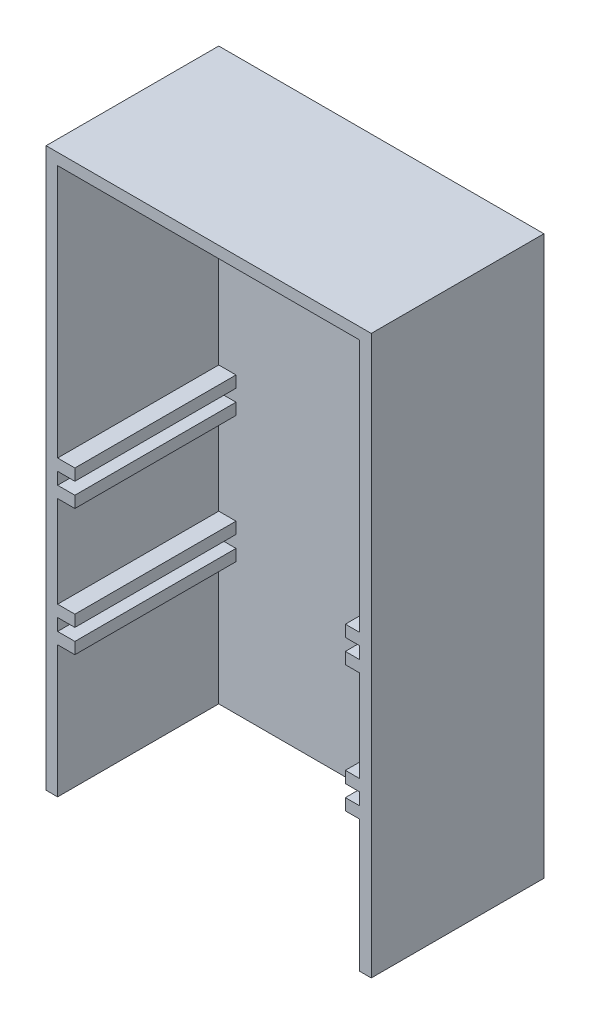
SolidWorks part; units mm, degrees
ref_plane "Front Plane" through (0, 0, 0) normal (0, 0, 1) x (1, 0, 0)
ref_plane "Top Plane" through (0, 0, 0) normal (0, 1, 0) x (1, 0, 0)
ref_plane "Right Plane" through (0, 0, 0) normal (1, 0, 0) x (0, 0, -1)
sketch "Sketch1" plane through (0, 0, 0) normal (0, 0, 1) x (1, 0, 0)
  line L1 (0, 0) -> (-56.5, 0)
  line L2 (0, 0) -> (0, 100)
  line L3 (0, 100) -> (-56.5, 100)
  line L4 (-56.5, 0) -> (-56.5, 100)
  dimension "D1" = 56.5
  dimension "D2" = 100
extrude "Boss-Extrude1" add sketch "Sketch1" along normal blind 30
shell "Shell1" thickness 2 removed face at (-28.25, 50, 30)
sketch "Sketch2" plane through (0, 0, 2) normal (0, 0, 1) x (1, 0, 0)
  line L0 (-54.5, 98) -> (-54.5, 2) construction
  line L1 (-54.5, 98) -> (-2, 98)
  line L2 (-54.5, 98) -> (-54.5, 96)
  line L3 (-54.5, 96) -> (-2, 96)
  line L4 (-2, 98) -> (-2, 96)
  line L5 (-2, 2) -> (-2, 98) construction
  line L7 (-2, 98) -> (-54.5, 98) construction
  dimension "D1" = 2
  dimension "D2" = 0
extrude "Boss-Extrude2" add sketch "Sketch2" along normal blind 26
sketch "Sketch3" plane through (0, 96, 0) normal (0, -1, 0) x (1, 0, 0)
  line L0 (-54.5, 28) -> (-2, 28) construction
  line L1 (-36.35, 28) -> (-20.15, 28)
  arc A0 (-20.15, 28) -> (-36.35, 28) centre (-28.25, 28) cw
  dimension "D1" = 8.1
extrude "Cut-Extrude5" cut sketch "Sketch3" against normal blind 3
sketch "Sketch6" plane through (-54.5, 0, 0) normal (1, 0, 0) x (0, 0, -1)
  line L0 (-30, 0) -> (-30, 100) construction
  line L1 (-30, 54) -> (0, 54)
  line L2 (-30, 54) -> (-30, 52)
  line L3 (-30, 52) -> (0, 52)
  line L4 (0, 54) -> (0, 52)
  line L5 (0, 0) -> (0, 100) construction
  line L8 (-30, 100) -> (0, 100) construction
  dimension "D1" = 2
  dimension "D2" = 46
extrude "Boss-Extrude3" add sketch "Sketch6" along normal blind 3
sketch "Sketch7" plane through (-54.5, 0, 0) normal (1, 0, 0) x (0, 0, -1)
  line L0 (-30, 0) -> (-30, 100) construction
  line L1 (-30, 49.9) -> (0, 49.9)
  line L2 (-30, 49.9) -> (-30, 47.9)
  line L3 (-30, 47.9) -> (0, 47.9)
  line L4 (0, 49.9) -> (0, 47.9)
  line L5 (0, 0) -> (0, 100) construction
  line L6 (-30, 52) -> (-2, 52) construction
  dimension "D1" = 2
  dimension "D2" = 2.1
extrude "Boss-Extrude4" add sketch "Sketch7" along normal blind 3
ref_plane "Plane1" through (-28, 0, 0) normal (1, 0, 0) x (0, 0, -1)
mirror "Mirror1" about plane through (-28, 0, 0) normal (1, 0, 0) of "Boss-Extrude4", "Boss-Extrude3"
ref_plane "Plane2" through (0, 39.95, 0) normal (0, -1, 0) x (-1, 0, 0)
mirror "Mirror2" about plane through (0, 39.95, 0) normal (0, -1, 0) of "Mirror1", "Boss-Extrude4", "Boss-Extrude3"
sketch "Sketch8" plane through (0, 0, 0) normal (0, -1, 0) x (1, 0, 0)
  line L1 (-56.5, 30) -> (0, 30)
  line L2 (-56.5, 30) -> (-56.5, 0)
  line L3 (-56.5, 0) -> (0, 0)
  line L4 (0, 30) -> (0, 0)
extrude "Cut-Extrude6" cut sketch "Sketch8" against normal blind 3
